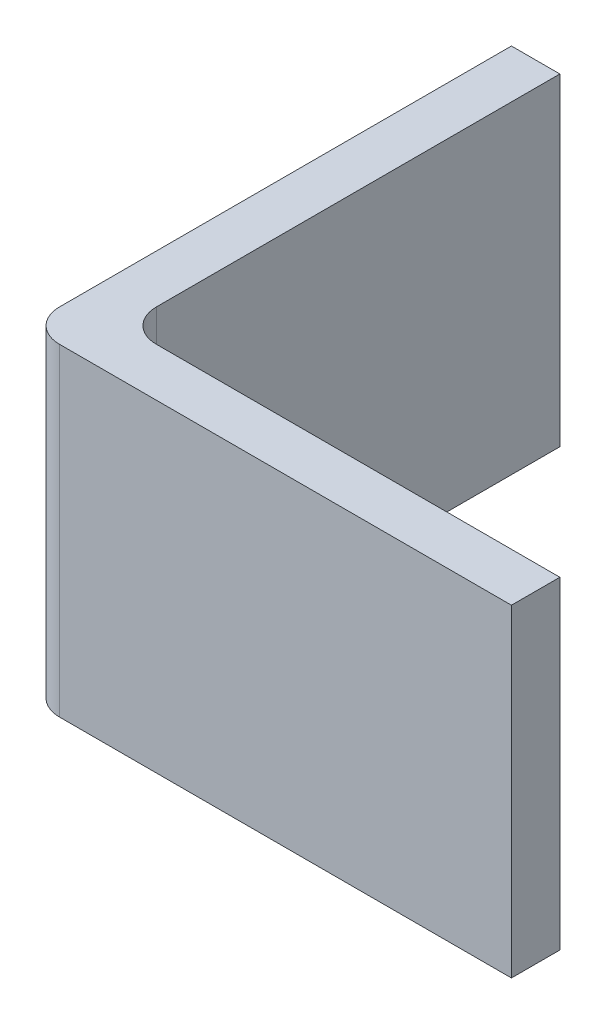
SolidWorks part; units mm, degrees
ref_plane "Спереди" through (0, 0, 0) normal (0, 0, 1) x (1, 0, 0)
ref_plane "Сверху" through (0, 0, 0) normal (0, 1, 0) x (1, 0, 0)
ref_plane "Справа" through (0, 0, 0) normal (1, 0, 0) x (0, 0, -1)
sketch "Эскиз1" plane through (0, 0, 0) normal (0, 1, 0) x (1, 0, 0)
  line L0 (0, 1) -> (0, 15)
  line L5 (0, 15) -> (1.5, 15)
  line L6 (1, 0) -> (15, 0)
  line L7 (15, 0) -> (15, 1.5)
  line L8 (15, 1.5) -> (2.5, 1.5)
  line L9 (1.5, 2.5) -> (1.5, 15)
  arc A0 (1, 0) -> (0, 1) centre (1, 1) cw
  arc A1 (2.5, 1.5) -> (1.5, 2.5) centre (2.5, 2.5) cw
  point P0 (0, 0)
  point P10 (0, 0)
  dimension "D5" = 1
  dimension "D1" = 15
  dimension "D2" = 1.5
  dimension "D3" = 15
  dimension "D4" = 1.5
extrude "Бобышка-Вытянуть1" add sketch "Эскиз1" along normal blind 10
sketch "Эскиз2" plane through (0, 0, 0) normal (0, 0, 1) x (1, 0, 0)
  line L0 (8.25, 0) -> (8.25, 11.3489) construction
  line L3 (1, 0) -> (15, 0) construction
  line L4 (15, 10) -> (15, 0) construction
  point P6 (7.5, 11.3489)
  dimension "D1" = 6.75
sketch "Эскиз3" plane through (0, 0, 0) normal (-1, 0, 0) x (0, 0, 1)
  line L0 (-8.25, 0) -> (-8.25, 11.1434) construction
  line L1 (-15, 0) -> (-1, 0) construction
  dimension "D1" = 6.75
